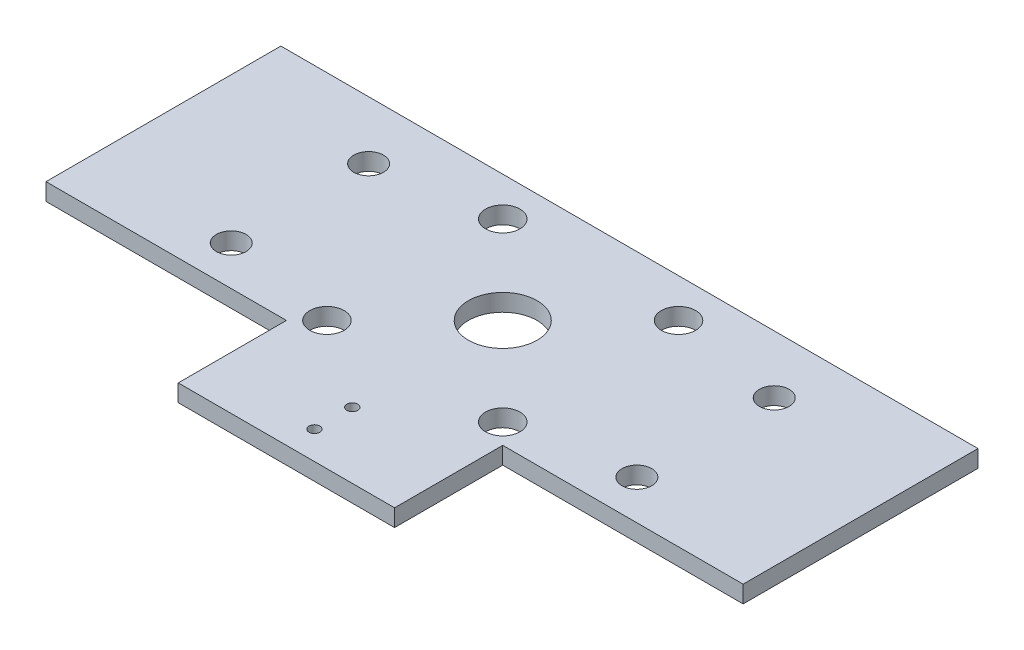
SolidWorks part; units mm, degrees
ref_plane "Front Plane" through (0, 0, 0) normal (0, 0, 1) x (1, 0, 0)
ref_plane "Top Plane" through (0, 0, 0) normal (0, 1, 0) x (1, 0, 0)
ref_plane "Right Plane" through (0, 0, 0) normal (1, 0, 0) x (0, 0, -1)
sketch "plateOutline" plane through (0, 0, 0) normal (0, 1, 0) x (1, 0, 0)
  line L0 (-40, 40) -> (-40, -40)
  line L1 (-40, -40) -> (40, -40)
  line L2 (-40, -40) -> (-40, 40)
  line L4 (40, -40) -> (40, 40)
  line L5 (-40, -40) -> (40, 40) construction
  line L6 (-40, 40) -> (40, -40) construction
  line L7 (-40, -40) -> (40, -40) construction
  line L8 (-40, -40) -> (-40, 40) construction
  line L9 (-40, 40) -> (40, 40) construction
  line L10 (40, -40) -> (40, 40) construction
  line L12 (-40, -40) -> (-128.9, -40)
  line L13 (-128.9, 40) -> (-128.9, -40)
  line L14 (40, 40) -> (40, -40)
  line L16 (40, -40) -> (128.9, -40)
  line L17 (128.9, 40) -> (128.9, -40)
  line L19 (-40, -40) -> (40, -40)
  line L20 (-40, -40) -> (-40, -80)
  line L21 (-40, -80) -> (40, -80)
  line L22 (40, -40) -> (40, -80)
  line L24 (-128.9, 40) -> (-128.9, 46.8499)
  line L25 (-128.9, 46.8499) -> (128.9, 46.8499)
  line L26 (128.9, 40) -> (128.9, 46.8499)
  point P0 (0, 0)
  dimension "D1" = 80
  dimension "D2" = 88.9
  dimension "D3" = 88.9
  dimension "D4" = 40
sketch "railGuides" plane through (0, 0, 0) normal (0, 1, 0) x (1, 0, 0)
  line L1 (-32.5, -32.5) -> (32.5, -32.5) construction
  line L2 (-32.5, -32.5) -> (-32.5, 32.5) construction
  line L3 (-32.5, 32.5) -> (32.5, 32.5) construction
  line L4 (32.5, -32.5) -> (32.5, 32.5) construction
  line L6 (-40, 40) -> (-25, 25) construction
  line L7 (40, 40) -> (25, 25) construction
  line L8 (25, -25) -> (40, -40) construction
  line L9 (-40, -40) -> (-25, -25) construction
  line L10 (-40, 40) -> (-25, 25) construction
  circle A0 centre (-32.5, 32.5) radius 6.35
  circle A1 centre (32.5, 32.5) radius 6.35
  circle A2 centre (32.5, -32.5) radius 6.35
  circle A3 centre (-32.5, -32.5) radius 6.35
sketch "FuelGrainMounting" plane through (0, 0, 0) normal (0, 1, 0) x (1, 0, 0)
  circle A0 centre (0, 0) radius 12.7
  dimension "D1" = 25.4
extrude "Boss-Extrude1" add sketch "plateOutline" along normal blind 6.35
extrude "Cut-Extrude1" cut sketch "railGuides" along normal blind 10
extrude "Cut-Extrude2" cut sketch "FuelGrainMounting" along normal blind 10
sketch "Sketch2" plane through (0, 0, 0) normal (0, 1, 0) x (1, 0, 0)
  line L0 (0, -69.63) -> (0, -55.63) construction
  line L1 (0, 0) -> (0, -69.63) construction
  circle A0 centre (0, -69.63) radius 2
  circle A1 centre (0, -55.63) radius 2
extrude "Cut-Extrude3" cut sketch "Sketch2" along normal blind 10
sketch "Sketch5" plane through (0, 0, 0) normal (0, 1, 0) x (1, 0, 0)
  circle A0 centre (-100, -0.0975) radius 10
  circle A1 centre (-64.45, -0.0975) radius 10
  circle A2 centre (64.45, 0) radius 10
  circle A3 centre (100, 0) radius 10
extrude "Cut-Extrude4" [suppressed] cut sketch "Sketch5" along normal blind 10
sketch "Sketch7" plane through (0, 6.35, 0) normal (0, 1, 0) x (1, 0, 0)
  line L0 (0, 0) -> (0, -69.63) construction
hole_wizard "M10 Clearance Hole1" positions "Sketch9" profile "Sketch8" hole size "M10" standard "ANSI Metric" end condition through all
sketch "Sketch9" plane through (0, 6.35, 0) normal (0, 1, 0) x (1, 0, 0)
  line L1 (-75, 25.4) -> (75, 25.4) construction
  line L2 (-75, 25.4) -> (-75, -25.4) construction
  line L3 (-75, -25.4) -> (75, -25.4) construction
  line L4 (75, 25.4) -> (75, -25.4) construction
  line L5 (-75, 25.4) -> (75, -25.4) construction
  line L6 (-75, -25.4) -> (75, 25.4) construction
  point P3 (75, -25.4)
  point P138 (-75, 25.4)
  point P139 (-75, -25.4)
  point P140 (75, 25.4)
  dimension "D1" = 150
  dimension "D2" = 50.8
sketch "Sketch8" plane through (75, 6.35, 25.4) normal (1, 0, 0) x (0, 0, 1)
  line L0 (0, 0) -> (0, 6.35)
  line L1 (0, 6.35) -> (5.5, 6.35)
  line L2 (5.5, 6.35) -> (5.5, 0)
  line L5 (5.5, 0) -> (0, 0)
  line L11 (0, -6.35) -> (0, 107.95) construction
  dimension "Thru Hole Dia." = 11
  dimension "Thru Hole Depth" = 6.35
